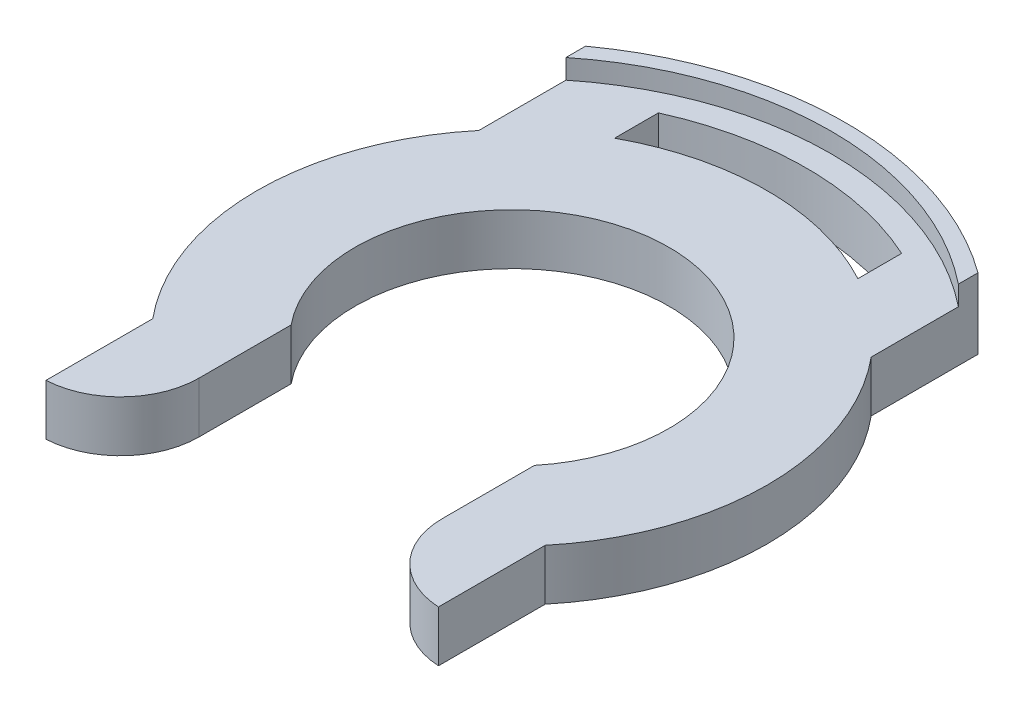
SolidWorks part; units mm, degrees
ref_plane "Front Plane" through (0, 0, 0) normal (0, 0, 1) x (1, 0, 0)
ref_plane "Top Plane" through (0, 0, 0) normal (0, 1, 0) x (1, 0, 0)
ref_plane "Right Plane" through (0, 0, 0) normal (1, 0, 0) x (0, 0, -1)
sketch "Sketch1" plane through (0, 0, 0) normal (0, 1, 0) x (1, 0, 0)
  line L1 (-34.3635, 21.3078) -> (-28.1635, 21.3078)
  line L2 (-34.3635, 21.3078) -> (-34.3635, -8.6366)
  line L3 (-34.3635, -8.6366) -> (-28.1635, -8.6366)
  line L4 (-28.1635, 21.3078) -> (-28.1635, -8.6366)
  line L5 (-34.3635, 21.3078) -> (-28.1635, -8.6366) construction
  line L6 (-34.3635, -8.6366) -> (-28.1635, 21.3078) construction
  line L7 (-36.2635, -11.117) -> (-26.2635, -11.117)
  line L8 (-36.2635, -11.117) -> (-36.2635, 23.7882)
  line L9 (-36.2635, 23.7882) -> (-26.2635, 23.7882)
  line L10 (-26.2635, -11.117) -> (-26.2635, 23.7882)
  line L11 (-36.2635, -11.117) -> (-26.2635, 23.7882) construction
  line L12 (-36.2635, 23.7882) -> (-26.2635, -11.117) construction
  circle A0 centre (-31.2635, 6.3356) radius 4
  circle A2 centre (-31.2635, 6.3356) radius 6.5
  circle A3 centre (-31.2635, 6.3356) radius 7.5
  circle A5 centre (-31.2635, 6.3356) radius 8.5
  dimension "D1" = 6.2
  dimension "D3" = 8
  dimension "D4" = 13
  dimension "D5" = 15
  dimension "D6" = 17
  dimension "D2" = 10
extrude "Boss-Extrude1" add sketch "Sketch1" along normal blind 1.3 contours L4 A3 L10 A2 | L4 A5 L10 A3 | L8 A5 L2 A3 | L8 A3 L2 A2 | L2 A2 L8 A0 | L8 A2 | L10 A2 | L4 A2 L2 A0 | L10 A3 L4 A2 | L10 A5 L4 A3 | L4 A5 L2 A3 | L2 A5 L8 A3 | L2 A3 L8 A2 | L4 A2 L10 A0 region at (-31.2635, 0, -14.1252) region at (-35.3399, 0, -13.1824) region at (-27.1871, 0, -13.1824) region at (-35.3529, 0, -11.963) region at (-27.174, 0, -11.963) region at (-31.2635, 0, -11.2108) region at (-35.3694, 0, -6.3356) region at (-35.3399, 0, 0.5112) region at (-27.1576, 0, -6.3356) region at (-36.8698, 0, -6.3356) region at (-35.3529, 0, -0.7083) region at (-25.6571, 0, -6.3356) region at (-27.1871, 0, 0.5112) region at (-27.174, 0, -0.7083)
fillet "Fillet1" radius 2 2 edges at (-34.3635, 0.65, 1.5789) (-28.1635, 0.65, 1.5789)
sketch "Sketch2" plane through (0, 1.3, 0) normal (0, 1, 0) x (1, 0, 0)
  line L0 (-36.2635, 10.4889) -> (-36.2635, 13.2095) construction
  line L1 (-26.2635, 10.4889) -> (-26.2635, 13.2095) construction
  line L2 (-26.2635, 12.7095) -> (-26.2635, 13.2095)
  line L3 (-36.2635, 12.7095) -> (-36.2635, 13.2095)
  arc A0 (-36.2635, 12.7095) -> (-26.2635, 12.7095) centre (-31.2635, 6.4645) cw
  arc A1 (-36.2635, 13.2095) -> (-26.2635, 13.2095) centre (-31.2635, 6.3356) cw
  point P0 (-36.2635, 12.7095)
  point P1 (-26.2635, 12.7095)
  point P14 (0, 0)
  dimension "D1" = 0.5
extrude "Boss-Extrude2" add sketch "Sketch2" along normal blind 0.5
